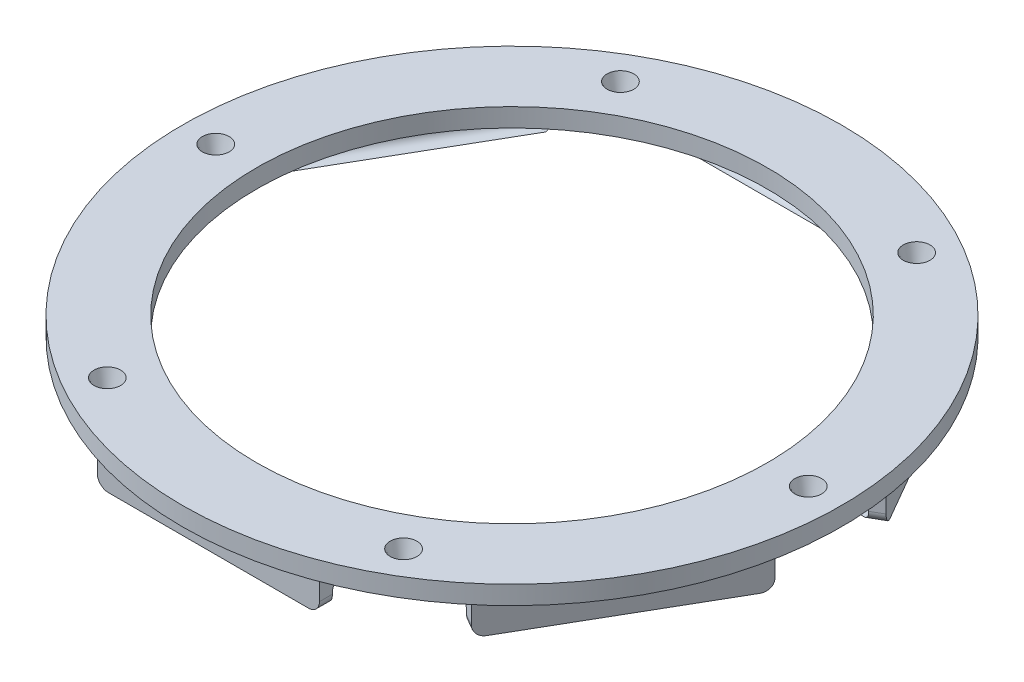
SolidWorks part; units mm, degrees
ref_plane "Front Plane" through (0, 0, 0) normal (0, 0, 1) x (1, 0, 0)
ref_plane "Top Plane" through (0, 0, 0) normal (0, 1, 0) x (1, 0, 0)
ref_plane "Right Plane" through (0, 0, 0) normal (1, 0, 0) x (0, 0, -1)
sketch "Sketch1" plane through (0, 0, 0) normal (0, 1, 0) x (1, 0, 0)
  line L0 (0, 0) -> (46.283, 0) construction
  line L1 (0, 0) -> (-20, 34.641) construction
  line L70 (0, 0) -> (0, 41) construction
  line L71 (43.8786, 0) -> (21.9393, 38) construction
  line L72 (21.9393, 38) -> (-21.9393, 38) construction
  line L73 (-21.9393, 38) -> (-43.8786, 0) construction
  line L74 (-43.8786, 0) -> (-21.9393, -38) construction
  line L75 (-21.9393, -38) -> (21.9393, -38) construction
  line L76 (21.9393, -38) -> (43.8786, 0) construction
  line L77 (-15, 41) -> (15, 41)
  line L78 (15, 41) -> (15, 38)
  line L79 (15, 38) -> (-15, 38)
  line L80 (-15, 38) -> (-15, 41)
  line L81 (25.409, 31.9904) -> (28.007, 33.4904)
  line L82 (28.007, 33.4904) -> (43.007, 7.5096)
  line L83 (43.007, 7.5096) -> (40.409, 6.0096)
  line L84 (47.3427, 0) -> (23.6714, 41) construction
  line L85 (23.6714, 41) -> (-23.6714, 41) construction
  line L86 (-23.6714, 41) -> (-47.3427, 0) construction
  line L87 (-47.3427, 0) -> (-23.6714, -41) construction
  line L88 (-23.6714, -41) -> (23.6714, -41) construction
  line L89 (23.6714, -41) -> (47.3427, 0) construction
  line L90 (40.409, 6.0096) -> (25.409, 31.9904)
  line L91 (40.409, -6.0096) -> (43.007, -7.5096)
  line L92 (43.007, -7.5096) -> (28.007, -33.4904)
  line L93 (28.007, -33.4904) -> (25.409, -31.9904)
  line L94 (25.409, -31.9904) -> (40.409, -6.0096)
  line L95 (15, -38) -> (15, -41)
  line L96 (15, -41) -> (-15, -41)
  line L97 (-15, -41) -> (-15, -38)
  line L98 (-15, -38) -> (15, -38)
  line L99 (-25.409, -31.9904) -> (-28.007, -33.4904)
  line L100 (-28.007, -33.4904) -> (-43.007, -7.5096)
  line L101 (-43.007, -7.5096) -> (-40.409, -6.0096)
  line L102 (-40.409, -6.0096) -> (-25.409, -31.9904)
  line L103 (-40.409, 6.0096) -> (-43.007, 7.5096)
  line L104 (-43.007, 7.5096) -> (-28.007, 33.4904)
  line L105 (-28.007, 33.4904) -> (-25.409, 31.9904)
  line L106 (-25.409, 31.9904) -> (-40.409, 6.0096)
  circle A0 centre (0, 0) radius 44.34
  circle A1 centre (0, 0) radius 40 construction
  circle A2 centre (-20, 34.641) radius 1.25
  circle A3 centre (0, 0) radius 38.87 construction
  circle A4 centre (20, 34.641) radius 1.25
  circle A5 centre (40, 0) radius 1.25
  circle A6 centre (20, -34.641) radius 1.25
  circle A7 centre (-20, -34.641) radius 1.25
  circle A8 centre (-40, 0) radius 1.25
  circle A9 centre (0, 0) radius 38
  circle A16 centre (0, 0) radius 38 construction
  circle A18 centre (0, 0) radius 41 construction
  point P10 (-19.435, 33.6624)
  point P36 (0, 0)
  point P47 (0, 0)
  point P59 (0, 41)
  point P84 (0, 0)
  point P98 (0, 0)
  dimension "D3" = 88.68
  dimension "D4" = 2.5
  dimension "D16" = 76
  dimension "D10" = 76
  dimension "D11" = 82
  dimension "D1" = 120
  dimension "D2" = 40
  dimension "D7" = 1.13
  dimension "D12" = 30
  dimension "D13" = 6
  dimension "D9" = 6
extrude "Boss-Extrude2" add sketch "Sketch1" along normal blind 1 and the other way blind 4.5 contours L98 L97 L96 L95
sketch "Sketch3" plane through (0, 0, 0) normal (0, 1, 0) x (1, 0, 0)
  line L0 (0, 0) -> (40, 0) construction
  line L1 (0, 0) -> (-20, 34.641) construction
  circle A0 centre (0, 0) radius 44.5
  circle A1 centre (0, 0) radius 34.5
  circle A2 centre (0, 0) radius 40 construction
  circle A3 centre (-20, 34.641) radius 1
  circle A4 centre (20, 34.641) radius 1
  circle A5 centre (40, 0) radius 1
  circle A6 centre (20, -34.641) radius 1
  circle A7 centre (-20, -34.641) radius 1
  circle A8 centre (-40, 0) radius 1
  point P21 (0, 0)
  dimension "D1" = 89
  dimension "D2" = 69
  dimension "D5" = 2
  dimension "D3" = 40
  dimension "D4" = 120
  dimension "D6" = 6
extrude "Boss-Extrude3" add sketch "Sketch3" along normal blind 2.5
chamfer "Chamfer1" distance 3 angle 15 6 edges at (20, 2.5, 35.641) (40, 2.5, 1) (20, 2.5, -33.641) (-20, 2.5, -33.641) (-40, 2.5, 1) (-20, 2.5, 35.641) first distance on face at (20, 2.5, 35.641) first distance on face at (40, 2.5, 1) first distance on face at (20, 2.5, -33.641) first distance on face at (-20, 2.5, -33.641) first distance on face at (-40, 2.5, 1) first distance on face at (-20, 2.5, 35.641)
fillet "Fillet1" radius 1.5 2 edges at (15, -4.5, 39.5) (-15, -4.5, 39.5)
hole_wizard "Ø1.0mm Dowel Slot1" positions "Sketch8" profile "Sketch7" size "Ø1.0" standard "ANSI Metric" slot yes end condition through all
sketch "Sketch8" plane through (-15, 0, 0) normal (-1, 0, 0) x (0, 0, 1)
  line L0 (38, -4.5) -> (38, -1.5) construction
  point P25 (38, -3)
  point P29 (38, -3)
  dimension "D1" = 3
sketch "Sketch7" plane through (-15, -3, 38) normal (0, 1, 0) x (0, 0, 1)
  line L0 (0, 0) -> (0, 59.5)
  line L1 (0, 59.5) -> (1.25, 59.5)
  line L2 (1.25, 59.5) -> (1.25, 0)
  line L5 (1.25, 0) -> (0, 0)
  line L11 (0, -6.35) -> (0, 107.95) construction
  dimension "Thru Hole Dia." = 2.5
  dimension "Thru Hole Depth" = 59.5
pattern_circular "CirPattern1" count 6 over 360 about axis through (0, 0, 0) along (0, 1, 0) of "Fillet1", "Boss-Extrude2", "Ø1.0mm Dowel Slot1"
